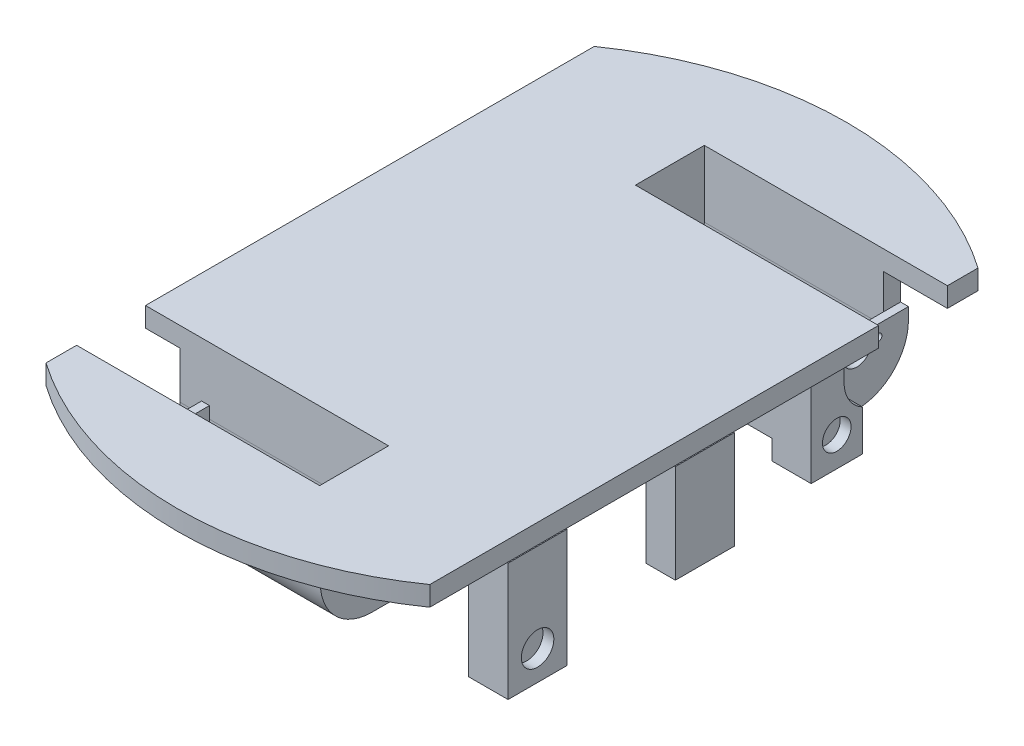
SolidWorks part; units mm, degrees
ref_plane "Front Plane" through (0, 0, 0) normal (0, 0, 1) x (1, 0, 0)
ref_plane "Top Plane" through (0, 0, 0) normal (0, 1, 0) x (1, 0, 0)
ref_plane "Right Plane" through (0, 0, 0) normal (1, 0, 0) x (0, 0, -1)
ref_axis "Center Axis" through (0, -34.25, 0) along (0, 1, 0)
sketch "Sketch1" plane through (0, 0, 0) normal (0, 1, 0) x (1, 0, 0)
  line L0 (-162.8746, 0) -> (178.0274, 0) construction
  line L1 (0, 86.4738) -> (0, -92.198) construction
  line L2 (-48.75, 69.6307) -> (-48.75, -69.6307)
  line L3 (48.75, 69.6307) -> (48.75, -69.6307)
  arc A0 (-48.75, 69.6307) -> (48.75, 69.6307) centre (0, 0) cw
  arc A1 (-48.75, -69.6307) -> (48.75, -69.6307) centre (0, 0) ccw
  dimension "D2" = 85
  dimension "D1" = 97.5
extrude "Base" add sketch "Sketch1" along normal blind 2.5 and the other way blind 2.5
sketch "Sketch2" plane through (0, -2.5, 0) normal (0, -1, 0) x (-1, 0, 0)
  line L0 (-133.3964, 0) -> (110.1594, 0) construction
  line L2 (41.5, -7.5) -> (49, -7.5)
  line L3 (41.5, -7.5) -> (41.5, 7.5)
  line L4 (41.5, 7.5) -> (49, 7.5)
  line L5 (49, -7.5) -> (49, 7.5)
  line L6 (0, -175.8738) -> (0, 153.5398) construction
  line L7 (7.5, -43.5) -> (-7.5, -43.5)
  line L8 (7.5, -43.5) -> (7.5, -36)
  line L9 (7.5, -36) -> (-7.5, -36)
  line L10 (-7.5, -43.5) -> (-7.5, -36)
  line L11 (-41.5, -7.5) -> (-49, -7.5)
  line L12 (-41.5, -7.5) -> (-41.5, 7.5)
  line L13 (-41.5, 7.5) -> (-49, 7.5)
  line L14 (-49, -7.5) -> (-49, 7.5)
  line L15 (7.5, 36) -> (-7.5, 36)
  line L16 (7.5, 36) -> (7.5, 43.5)
  line L17 (7.5, 43.5) -> (-7.5, 43.5)
  line L18 (-7.5, 36) -> (-7.5, 43.5)
  dimension "D1" = 15
  dimension "D2" = 7.5
  dimension "D3" = 36
  dimension "D4" = 41.5
  dimension "D5" = 41.5
  dimension "D6" = 36
  dimension "D7" = 7.5
  dimension "D8" = 7.5
  dimension "D9" = 7.5
  dimension "D10" = 15
  dimension "D11" = 15
  dimension "D12" = 15
extrude "BatteryHolder" add sketch "Sketch2" along normal blind 25
sketch "Sketch3" plane through (0, -27.5, 0) normal (0, -1, 0) x (-1, 0, 0)
  circle A0 centre (45.5, 0) radius 1.625
  circle A1 centre (0, -40) radius 1.625
  circle A2 centre (-45.5, 0) radius 1.625
  circle A3 centre (0, 40) radius 1.625
  dimension "D1" = 3.25
  dimension "D2" = 3.25
  dimension "D3" = 3.25
  dimension "D4" = 3.25
  dimension "D5" = 40
  dimension "D6" = 40
  dimension "D7" = 45.5
  dimension "D8" = 45.5
extrude "Cut-Extrude1" cut sketch "Sketch3" against normal blind 10
sketch "Sketch5" plane through (0, -2.5, 0) normal (0, -1, 0) x (-1, 0, 0)
  line L0 (-7.5, 36) -> (7.5, 36) construction
  line L1 (40, -49) -> (30, -49)
  line L2 (40, -49) -> (40, -36)
  line L3 (40, -36) -> (30, -36)
  line L4 (30, -49) -> (30, -36)
  line L5 (-30, 36) -> (-40, 36)
  line L6 (-30, 36) -> (-30, 49)
  line L7 (-30, 49) -> (-40, 49)
  line L8 (-40, 36) -> (-40, 49)
  line L9 (7.5, -36) -> (-7.5, -36) construction
  line L10 (-130.245, 42.5) -> (155.6892, 42.5) construction
  line L12 (155.6892, -42.5) -> (-162.2503, -42.5) construction
  line L14 (-162.2503, 0) -> (191.3178, 0) construction
  dimension "D1" = 85
  dimension "D2" = 30
  dimension "D3" = 30
  dimension "D4" = 10
  dimension "D5" = 10
extrude "Boss-Extrude2" add sketch "Sketch5" along normal blind 30
sketch "Sketch6" plane through (-40, 0, 0) normal (-1, 0, 0) x (0, 0, 1)
  line L0 (42.5, -32.5) -> (42.5, -2.5) construction
  line L2 (49, -2.5) -> (36, -2.5) construction
  line L4 (36, -32.5) -> (36, -2.5) construction
  line L5 (49, -32.5) -> (49, -2.5) construction
  circle A0 centre (42.5, -25) radius 3.625
  dimension "D1" = 7.25
  dimension "D2" = 22.5
extrude "Cut-Extrude2" cut sketch "Sketch6" against normal blind 2.75
sketch "Sketch7" plane through (40, 0, 0) normal (1, 0, 0) x (0, 0, -1)
  line L0 (42.5, -32.5) -> (42.5, -2.5) construction
  line L1 (49, -32.5) -> (36, -32.5) construction
  line L2 (49, -2.5) -> (36, -2.5) construction
  circle A0 centre (42.5, -25) radius 3.625
  dimension "D2" = 7.25
  dimension "D1" = 22.5
extrude "Cut-Extrude3" cut sketch "Sketch7" against normal blind 2.75
sketch "Sketch12" plane through (0, -2.5, 0) normal (0, -1, 0) x (-1, 0, 0)
  line L0 (30, -49) -> (32.5, -49)
  line L1 (30, -49) -> (40, -49) construction
  line L2 (32.5, -49) -> (32.5, -68.5)
  line L3 (-17.5, -68.5) -> (32.5, -68.5)
  line L5 (30, -36) -> (30, -49) construction
  line L8 (30, -36) -> (30, -49)
  line L9 (7.5, -43.5) -> (7.5, -36) construction
  line L10 (-7.5, -43.5) -> (7.5, -43.5) construction
  line L11 (-7.5, -36) -> (-7.5, -43.5) construction
  line L12 (7.5, -43.5) -> (7.5, -36)
  line L13 (-7.5, -43.5) -> (7.5, -43.5)
  line L14 (-7.5, -36) -> (-7.5, -43.5)
  line L15 (7.5, -36) -> (30, -36)
  line L16 (-7.5, -36) -> (-17.5, -36)
  line L17 (-17.5, -36) -> (-17.5, -68.5)
  dimension "D1" = 32.5
  dimension "D2" = 10
  dimension "D3" = 2.5
extrude "Boss-Extrude4" add sketch "Sketch12" along normal up to surface (25 mm away) up to face at (0, -27.5, 38.375)
sketch "Sketch11" plane through (0, 0, 0) normal (1, 0, 0) x (0, 0, -1)
  line L0 (-44.3566, -14.3934) -> (-44.3566, 2.5)
  line L2 (-44.3566, 2.5) -> (-61.8566, 2.5)
  line L3 (-61.8566, 2.5) -> (-61.8566, -14.3934)
  line L5 (-39.2149, -28.2851) -> (-65.2384, -2.2616) construction
  line L7 (-69.6307, 2.5) -> (-85, 2.5) construction
  line L8 (0, 86.9309) -> (0, -106.9577) construction
  arc A0 (-61.8566, -14.3934) -> (-44.3566, -14.3934) centre (-53.1066, -14.3934) ccw
  circle A2 centre (-42.5, -25) radius 3.625 construction
  circle A3 centre (-42.5, -25) radius 3.625 construction
  dimension "D3" = 8.75
  dimension "D1" = 15
  dimension "D2" = 45
extrude "Cut-Extrude6" cut sketch "Sketch11" against normal blind 50 and the other way blind 13
sketch "Sketch13" plane through (-32.5, 0, 0) normal (-1, 0, 0) x (0, 0, 1)
  line L4 (68.5, -27.5) -> (49, -27.5) construction
  line L5 (66.2132, -14.3934) -> (66.2132, -2.5)
  line L8 (66.2132, -2.5) -> (68.5, -2.5)
  line L9 (68.5, -2.5) -> (61.8566, -2.5) construction
  line L10 (68.5, -2.5) -> (68.5, -27.5)
  line L11 (68.5, -27.5) -> (53.1066, -27.5)
  arc A0 (53.1066, -27.5) -> (66.2132, -14.3934) centre (53.1066, -14.3934) ccw
  point P5 (0, 0)
extrude "Cut-Extrude7" cut sketch "Sketch13" against normal up to next
sketch "Sketch14" plane through (-32.5, 0, 0) normal (-1, 0, 0) x (0, 0, 1)
  line L0 (53.1066, -27.5) -> (49, -27.5) construction
  line L1 (66.2132, -2.5) -> (66.2132, -14.3934) construction
  line L2 (49, -27.5) -> (49, -22.1199)
  line L3 (44.3566, -11.3934) -> (49.3566, -11.3934)
  line L4 (49.3566, -11.3934) -> (49.3566, -14.3934)
  line L5 (56.8566, -14.3934) -> (56.8566, -11.3934)
  line L6 (56.8566, -11.3934) -> (66.2132, -11.3934)
  line L7 (66.2132, -11.3934) -> (66.2132, -14.3934)
  line L9 (44.3566, -14.3934) -> (44.3566, -11.3934)
  line L10 (49, -27.5) -> (53.1066, -27.5)
  arc A0 (49.3566, -14.3934) -> (56.8566, -14.3934) centre (53.1066, -14.3934) ccw
  arc A1 (66.2132, -14.3934) -> (53.1066, -27.5) centre (53.1066, -14.3934) cw
  arc A2 (53.1066, -27.5) -> (66.2132, -14.3934) centre (53.1066, -14.3934) ccw construction
  arc A3 (49, -22.1199) -> (61.8566, -14.3934) centre (53.1066, -14.3934) ccw construction
  arc A4 (44.3566, -14.3934) -> (61.8566, -14.3934) centre (53.1066, -14.3934) ccw construction
  arc A6 (49, -22.1199) -> (44.3566, -14.3934) centre (53.1066, -14.3934) cw
  arc A7 (44.3566, -14.3934) -> (49, -22.1199) centre (53.1066, -14.3934) ccw construction
  dimension "D1" = 3
  dimension "D2" = 7.5
extrude "Boss-Extrude5" add sketch "Sketch14" along normal blind 2
sketch "Sketch15" plane through (-34.5, 0, 0) normal (-1, 0, 0) x (0, 0, 1)
  line L0 (47.6066, -14.3934) -> (58.6066, -14.3934) construction
  circle A0 centre (58.6066, -14.3934) radius 0.875
  circle A1 centre (47.6066, -14.3934) radius 0.875
  arc A2 (49.3566, -14.3934) -> (56.8566, -14.3934) centre (53.1066, -14.3934) ccw construction
  arc A3 (49.3566, -14.3934) -> (56.8566, -14.3934) centre (53.1066, -14.3934) ccw construction
  dimension "D1" = 1.75
  dimension "D2" = 1.75
  dimension "D3" = 11
extrude "Cut-Extrude8" cut sketch "Sketch15" against normal up to next
sketch "Sketch16" plane through (0, 0, 36) normal (0, 0, -1) x (-1, 0, 0)
  line L0 (0, 14.1041) -> (0, -56.6149) construction
  line L1 (3, -25.5) -> (-3, -25.5)
  line L2 (3, -25.5) -> (3, -23)
  line L3 (3, -23) -> (-3, -23)
  line L4 (-3, -25.5) -> (-3, -23)
  line L5 (7.5, -27.5) -> (-7.5, -27.5) construction
  dimension "D1" = 2
  dimension "D2" = 6
  dimension "D3" = 2.5
extrude "NutCut" cut sketch "Sketch16" against normal blind 10
sketch "Sketch17" plane through (0, -2.5, 0) normal (0, -1, 0) x (-1, 0, 0)
  line L0 (-49, 7.5) -> (-49, -7.5) construction
  line L1 (-49, -50) -> (-39, -50)
  line L2 (-49, -50) -> (-49, -35)
  line L3 (-49, -35) -> (-39, -35)
  line L4 (-39, -50) -> (-39, -35)
  line L5 (-121.7994, -42.5) -> (-23.7999, -42.5) construction
  dimension "D1" = 42.5
  dimension "D2" = 15
  dimension "D3" = 10
extrude "Boss-Extrude6" add sketch "Sketch17" along normal blind 30
sketch "Sketch18" plane through (49, 0, 0) normal (1, 0, 0) x (0, 0, -1)
  line L0 (-42.5, -7.6315) -> (-42.5, -33.0073) construction
  line L1 (-35, -32.5) -> (-35, -2.5) construction
  line L2 (-50, -32.5) -> (-50, -2.5) construction
  line L4 (69.6307, -2.5) -> (7.5, -2.5) construction
  circle A0 centre (-42.5, -25) radius 4.125
  dimension "D1" = 8.25
  dimension "D2" = 22.5
extrude "Cut-Extrude11" cut sketch "Sketch18" against normal blind 2.75
pattern_circular "CirPattern2" count 2 over 360 about axis through (0, -34.25, 0) along (0, 1, 0) of "Boss-Extrude4", "Cut-Extrude6", "Cut-Extrude7", "Boss-Extrude5", "Cut-Extrude8"
